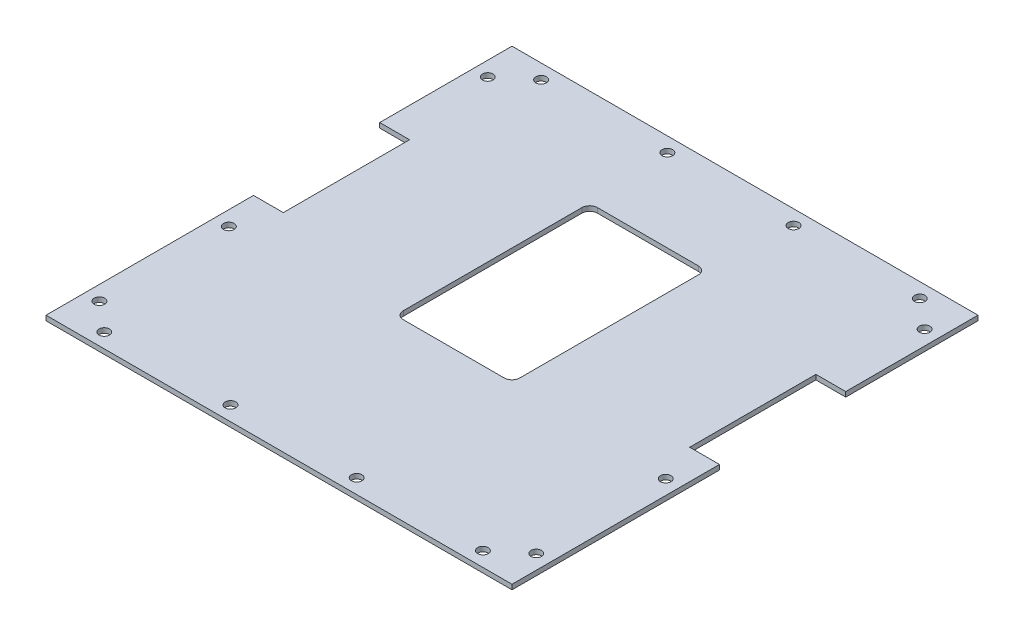
SolidWorks part; units mm, degrees
ref_plane "Front Plane" through (0, 0, 0) normal (0, 0, 1) x (1, 0, 0)
ref_plane "Top Plane" through (0, 0, 0) normal (0, 1, 0) x (1, 0, 0)
ref_plane "Right Plane" through (0, 0, 0) normal (1, 0, 0) x (0, 0, -1)
sketch "Sketch2" plane through (0, 0, 0) normal (0, 1, 0) x (1, 0, 0)
  line L0 (0, 0) -> (152.4, 0)
  line L1 (152.4, 0) -> (152.4, 152.4)
  line L2 (152.4, 152.4) -> (0, 152.4)
  line L3 (0, 152.4) -> (0, 0)
  dimension "D1" = 152.4
  dimension "D2" = 152.4
extrude "Boss-Extrude1" add sketch "Sketch2" along normal blind 1.5875
sketch "Sketch3" plane through (0, 1.5875, 0) normal (0, 1, 0) x (1, 0, 0)
  line L0 (0, 152.4) -> (4.7625, 152.4)
  line L1 (152.4, 152.4) -> (0, 152.4) construction
  line L2 (4.7625, 152.4) -> (4.7625, 0)
  line L3 (0, 0) -> (152.4, 0) construction
  line L4 (0, 152.4) -> (0, 147.6375)
  line L5 (0, 152.4) -> (0, 0) construction
  line L6 (0, 147.6375) -> (152.4, 147.6375)
  line L7 (152.4, 0) -> (152.4, 152.4) construction
  line L8 (152.4, 152.4) -> (147.6375, 152.4)
  line L9 (147.6375, 152.4) -> (147.6375, 0)
  line L10 (152.4, 0) -> (152.4, 4.7625)
  line L11 (152.4, 4.7625) -> (0, 4.7625)
  point P21 (4.7625, 139.7)
  point P23 (14.2875, 147.6375)
  point P24 (147.6375, 139.7)
  point P25 (138.1125, 4.7625)
  point P26 (4.7625, 12.7)
  dimension "D1" = 4.7625
  dimension "D2" = 4.7625
  dimension "D3" = 4.7625
  dimension "D4" = 4.7625
  dimension "D5" = 12.7
  dimension "D6" = 14.2875
  dimension "D7" = 12.7
  dimension "D8" = 14.2875
  dimension "D9" = 12.7
sketch "Sketch4" plane through (0, 1.5875, 0) normal (0, 1, 0) x (1, 0, 0)
  point P0 (14.2875, 147.6375)
  point P3 (147.6375, 139.7)
  point P6 (138.1125, 4.7625)
  point P9 (4.7625, 12.7)
sketch "Sketch6" plane through (0, 1.5875, 0) normal (0, 1, 0) x (1, 0, 0)
  line L0 (152.4, 4.7625) -> (0, 4.7625) construction
  line L1 (0, 152.4) -> (0, 0) construction
  point P0 (14.2875, 147.6375)
  point P3 (14.2875, 4.7625)
  dimension "D1" = 14.2875
hole_wizard "#5 Clearance Hole2" positions "Sketch6" profile "Sketch7" hole size "#5" standard "ANSI Inch" end condition through all
sketch "Sketch7" plane through (14.2875, 1.5875, -147.6375) normal (1, 0, 0) x (0, 0, 1)
  line L0 (0, 0) -> (0, 1.5875)
  line L1 (0, 1.5875) -> (1.7272, 1.5875)
  line L2 (1.7272, 1.5875) -> (1.7272, 0)
  line L5 (1.7272, 0) -> (0, 0)
  line L11 (0, -6.35) -> (0, 107.95) construction
  dimension "Thru Hole Dia." = 3.4544
  dimension "Thru Hole Depth" = 1.5875
sketch "Sketch8" plane through (0, 1.5875, 0) normal (0, 1, 0) x (1, 0, 0)
  point P0 (4.7625, 139.7)
  point P3 (147.6375, 139.7)
hole_wizard "#5 Clearance Hole3" positions "Sketch8" profile "Sketch9" hole size "#5" standard "ANSI Inch" end condition through all
sketch "Sketch9" plane through (4.7625, 1.5875, -139.7) normal (1, 0, 0) x (0, 0, 1)
  line L0 (0, 0) -> (0, 1.5875)
  line L1 (0, 1.5875) -> (1.7272, 1.5875)
  line L2 (1.7272, 1.5875) -> (1.7272, 0)
  line L5 (1.7272, 0) -> (0, 0)
  line L11 (0, -6.35) -> (0, 107.95) construction
  dimension "Thru Hole Dia." = 3.4544
  dimension "Thru Hole Depth" = 1.5875
pattern_linear "LPattern1" count 4 spacing 42.3333 along (0, 0, 1) skipping (1, 0) of "#5 Clearance Hole3"
pattern_linear "LPattern2" count 4 spacing 41.275 along (1, 0, 0) of "#5 Clearance Hole2"
sketch "Sketch12" plane through (0, 1.5875, 0) normal (0, 1, 0) x (1, 0, 0)
  line L10 (0, 152.4) -> (0, 0) construction
  line L11 (57.15, 120.65) -> (95.25, 120.65)
  line L12 (57.15, 120.65) -> (57.15, 57.15)
  line L13 (57.15, 57.15) -> (95.25, 57.15)
  line L14 (95.25, 120.65) -> (95.25, 57.15)
  line L15 (152.4, 152.4) -> (0, 152.4) construction
  line L16 (152.4, 0) -> (152.4, 152.4) construction
  dimension "D1" = 57.15
  dimension "D2" = 31.75
  dimension "D3" = 57.15
  dimension "D4" = 63.5
extrude "Cut-Extrude1" cut sketch "Sketch12" against normal blind 2.54 contours L14 L12 region at (76.2, 1.5875, -88.9)
fillet "Fillet2" radius 2.54 4 edges at (95.25, 0.7937, -57.15) (57.15, 0.7937, -57.15) (57.15, 0.7937, -120.65) (95.25, 0.7937, -120.65)
sketch "Sketch13" plane through (0, 1.5875, 0) normal (0, 1, 0) x (1, 0, 0)
  line L0 (152.4, 0) -> (152.4, 152.4) construction
  line L1 (152.4, 109.14) -> (142.65, 109.14)
  line L2 (152.4, 109.14) -> (152.4, 67.86)
  line L3 (152.4, 67.86) -> (142.65, 67.86)
  line L4 (142.65, 109.14) -> (142.65, 67.86)
  line L5 (152.4, 152.4) -> (0, 152.4) construction
  line L6 (76.2, 152.4) -> (76.2, 0) construction
  line L7 (0, 0) -> (152.4, 0) construction
  line L8 (0, 67.86) -> (9.75, 67.86)
  line L9 (9.75, 109.14) -> (9.75, 67.86)
  line L10 (0, 109.14) -> (9.75, 109.14)
  line L11 (0, 109.14) -> (0, 67.86)
  point P8 (147.525, 67.86)
  dimension "D1" = 43.26
  dimension "D2" = 41.28
  dimension "D3" = 9.75
extrude "Cut-Extrude2" cut sketch "Sketch13" against normal through all
